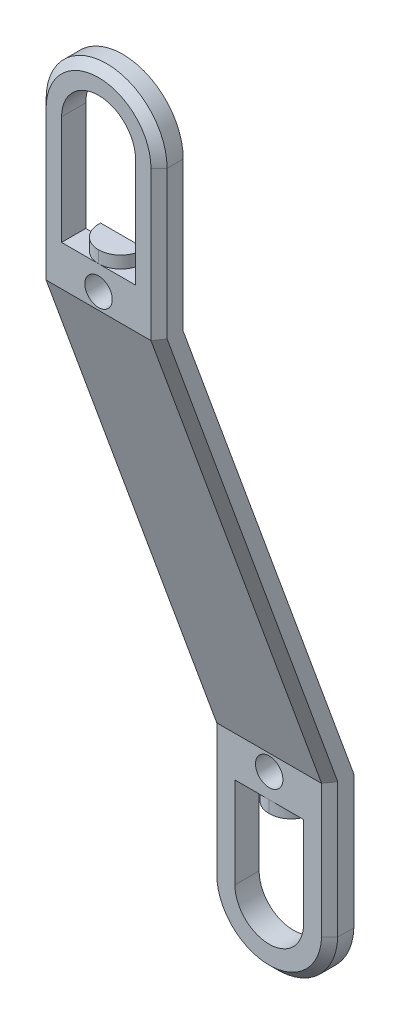
SolidWorks part; units mm, degrees
ref_plane "Front Plane" through (0, 0, 0) normal (0, 0, 1) x (1, 0, 0)
ref_plane "Top Plane" through (0, 0, 0) normal (0, 1, 0) x (1, 0, 0)
ref_plane "Right Plane" through (0, 0, 0) normal (1, 0, 0) x (0, 0, -1)
sketch "Sketch1" plane through (0, 0, 0) normal (0, 0, 1) x (1, 0, 0)
  line L0 (0, 42.5) -> (0, -42.5) construction
  line L1 (0, -14.3865) -> (0, 14.3865) construction
  line L2 (7.5, 42.5) -> (7.5, -42.5)
  line L3 (-7.5, 42.5) -> (-7.5, -42.5)
  line L4 (8.25, 0) -> (-8.25, 0) construction
  arc A0 (7.5, 42.5) -> (-7.5, 42.5) centre (0, 42.5) ccw
  arc A1 (-7.5, -42.5) -> (7.5, -42.5) centre (0, -42.5) ccw
  point P5 (0, 0)
  point P10 (0, 50)
  point P11 (0, -50)
  dimension "D1" = 100
  dimension "D2" = 15
extrude "Boss-Extrude1" add sketch "Sketch1" along normal blind 3
sketch "Sketch2" plane through (0, 0, 3) normal (0, 0, 1) x (1, 0, 0)
  line L0 (0, -14.3865) -> (0, 14.3865) construction
  line L1 (-4.585, 42.5) -> (-4.585, 29)
  line L2 (-4.585, 29) -> (4.585, 29)
  line L3 (4.585, 29) -> (4.585, 42.5)
  arc A0 (4.585, 42.5) -> (-4.585, 42.5) centre (0, 42.5) ccw
  arc A1 (7.5, 42.5) -> (-7.5, 42.5) centre (0, 42.5) ccw construction
  dimension "D1" = 13.5
extrude "Cut-Extrude1" cut sketch "Sketch2" against normal up to next
sketch "Sketch3" plane through (0, 29, 0) normal (0, 1, 0) x (1, 0, 0)
  line L0 (4.585, 0) -> (-4.585, 0) construction
  line L1 (-2.75, 0) -> (2.75, 0)
  line L2 (-2.75, 0) -> (-2.75, -3)
  line L3 (-2.75, -3) -> (2.75, -3)
  line L4 (2.75, 0) -> (2.75, -3)
  line L5 (-4.585, -3) -> (4.585, -3) construction
  line L6 (0, -14.3865) -> (0, 14.3865) construction
  point P8 (0, 0)
  dimension "D1" = 5.5
extrude "Boss-Extrude2" add sketch "Sketch3" along normal blind 1.5
mirror "Mirror1" about plane through (0, 0, 0) normal (0, 1, 0) of "Boss-Extrude2", "Cut-Extrude1"
sketch "Sketch4" plane through (0, 0, 0) normal (1, 0, 0) x (0, 0, -1)
  line L1 (-6.851, 24) -> (0, 24)
  line L2 (-6.851, 24) -> (-6.851, -55.5038)
  line L3 (-6.851, -55.5038) -> (0, -55.5038)
  line L4 (0, 24) -> (0, -55.5038)
  line L5 (0, 8.25) -> (0, -8.25) construction
  dimension "D1" = 5
extrude "Cut-Extrude2" cut sketch "Sketch4" against normal up to next and the other way up to next
sketch "Sketch5" plane through (0, 0, 0) normal (1, 0, 0) x (0, 0, -1)
  line L0 (0, 24) -> (21.1574, -34.1294)
  line L2 (-3, 24) -> (0, 24) construction
  line L3 (21.1574, -34.1294) -> (18.1574, -34.1294)
  line L4 (18.1574, -34.1294) -> (-3, 24)
  line L5 (-3, 24) -> (0, 24)
  line L6 (-3, 24) -> (-3, 42.5) construction
  dimension "D1" = 20
extrude "Boss-Extrude3" add sketch "Sketch5" along normal up to surface (7.5 mm away) and the other way up to vertex (7.5 mm away) up to face at (7.5, 33.25, 1.5) other way up to point (-7.5, 24, 0)
sketch "Sketch6" plane through (0, -34.1294, 0) normal (0, -1, 0) x (1, 0, 0)
  line L4 (-7.5, -21.1574) -> (7.5, -21.1574)
  line L5 (7.5, -21.1574) -> (7.5, -18.1574)
  line L6 (7.5, -18.1574) -> (-7.5, -18.1574)
  line L7 (-7.5, -18.1574) -> (-7.5, -21.1574)
  line L8 (-7.5, -21.1574) -> (7.5, -21.1574)
  line L9 (7.5, -21.1574) -> (7.5, -18.1574)
  line L10 (7.5, -18.1574) -> (-7.5, -18.1574)
  line L11 (-7.5, -18.1574) -> (-7.5, -21.1574)
  dimension "D1" = 0
ref_plane "Plane1" through (0, 0, -21.1574) normal (0, 0, 1) x (1, 0, 0)
sketch "Sketch7" plane through (0, 0, -21.1574) normal (0, 0, 1) x (1, 0, 0)
  line L0 (7.5, -34.1294) -> (7.5, -50.6294)
  line L1 (-7.5, -34.1294) -> (-7.5, -50.3954)
  line L6 (7.5, 24) -> (-7.5, 24)
  line L7 (7.5, -34.1294) -> (7.5, 24)
  line L8 (-7.5, -34.1294) -> (7.5, -34.1294)
  line L9 (-7.5, 24) -> (-7.5, -34.1294)
  line L12 (-7.5, -34.1294) -> (7.5, -34.1294)
  arc A0 (-7.5, -50.3954) -> (7.5, -50.6294) centre (0.0018, -50.3954) ccw
  dimension "D2" = 16.5
  dimension "D1" = 0
extrude "Boss-Extrude5" add sketch "Sketch7" along normal up to vertex (3 mm away) up to point (7.5, -34.1294, -18.1574)
sketch "Sketch9" plane through (0, 0, -21.1574) normal (0, 0, -1) x (-1, 0, 0)
  line L0 (-4.25, -39.1294) -> (4.25, -39.1294)
  line L1 (4.25, -39.1294) -> (4.25, -50.3954)
  line L3 (-4.25, -39.1294) -> (-4.2536, -50.394)
  line L4 (-7.5, -34.1294) -> (7.5, -34.1294) construction
  arc A0 (-4.2536, -50.394) -> (4.25, -50.3954) centre (-0.0018, -50.3954) ccw
  arc A2 (-7.5, -50.6294) -> (7.5, -50.3954) centre (-0.0018, -50.3954) ccw construction
  dimension "D1" = 8.5
  dimension "D3" = 5
extrude "Cut-Extrude3" cut sketch "Sketch9" against normal up to next
sketch "Sketch10" plane through (0, -39.1294, 0) normal (0, -1, 0) x (1, 0, 0)
  line L0 (-4.25, -18.1574) -> (4.25, -18.1574) construction
  line L1 (-2.75, -18.1574) -> (2.75, -18.1574)
  line L2 (-2.75, -18.1574) -> (-2.75, -21.1574)
  line L3 (-2.75, -21.1574) -> (2.75, -21.1574)
  line L4 (2.75, -18.1574) -> (2.75, -21.1574)
  line L5 (-4.25, -21.1574) -> (4.25, -21.1574) construction
  point P8 (0, -18.1574)
  point P9 (0, -18.1574)
  dimension "D1" = 5.5
extrude "Boss-Extrude6" add sketch "Sketch10" along normal blind 1.5
sketch "Sketch11" plane through (0, 0, 3) normal (0, 0, 1) x (1, 0, 0)
  line L0 (7.5, 24) -> (7.5, 42.5) construction
  line L1 (-7.5, 42.5) -> (-7.5, 24) construction
  line L2 (7.5, 24) -> (7.5, 42.5)
  line L3 (-7.5, 42.5) -> (-7.5, 24)
  line L4 (-5.5, 28) -> (5.5, 28)
  line L5 (5.5, 24) -> (5.5, 42.5)
  line L6 (-5.5, 42.5) -> (-5.5, 24)
  line L7 (5.5, 28) -> (5.5, 42.5)
  line L8 (-5.5, 42.5) -> (-5.5, 28)
  line L9 (7.5, 24) -> (-7.5, 24) construction
  line L10 (7.5, 24) -> (-7.5, 24)
  line L11 (-4.585, 29) -> (-2.75, 29) construction
  arc A0 (7.5, 42.5) -> (-7.5, 42.5) centre (0, 42.5) ccw construction
  arc A1 (7.5, 42.5) -> (-7.5, 42.5) centre (0, 42.5) ccw
  arc A4 (5.5, 42.5) -> (-5.5, 42.5) centre (0, 42.5) ccw
  arc A5 (5.5, 42.5) -> (-5.5, 42.5) centre (0, 42.5) ccw
  dimension "D2" = 1
  dimension "D1" = 2
extrude "Boss-Extrude7" [suppressed] add sketch "Sketch11" along normal blind 2
sketch "Sketch12" plane through (0, 0, -18.1574) normal (0, 0, 1) x (1, 0, 0)
  line L0 (-5.5, -38.1294) -> (-5.5, -50.3954)
  line L1 (5.5, -50.5957) -> (5.5, -38.1294)
  line L2 (-5.5, -38.1294) -> (5.5, -38.1294)
  line L3 (7.5, -34.1294) -> (-7.5, -34.1294)
  line L4 (-7.5, -34.1294) -> (-7.5, -50.3954)
  line L5 (7.5, -50.6294) -> (7.5, -34.1294)
  line L6 (7.5, -34.1294) -> (-7.5, -34.1294)
  line L7 (-7.5, -34.1294) -> (-7.5, -50.3954)
  line L8 (7.5, -50.6294) -> (7.5, -34.1294)
  line L9 (-5.5, -34.1294) -> (-5.5, -50.3954) construction
  line L10 (5.5, -50.5957) -> (5.5, -34.1294) construction
  line L11 (-4.25, -39.1294) -> (-2.75, -39.1294) construction
  arc A0 (-5.5, -50.3954) -> (5.5, -50.5957) centre (0.0018, -50.3954) ccw
  arc A1 (-7.5, -50.3954) -> (7.5, -50.6294) centre (0.0018, -50.3954) ccw
  arc A2 (-7.5, -50.3954) -> (7.5, -50.6294) centre (0.0018, -50.3954) ccw
  dimension "D3" = 1
  dimension "D1" = 0
  dimension "D2" = 2
extrude "Boss-Extrude8" [suppressed] add sketch "Sketch12" along normal blind 2
sketch "Sketch13" [suppressed] plane through (-7.5, 0, 0) normal (-1, 0, 0) x (0, 0, 1)
  line L0 (5, 24) -> (-16.1574, -34.1294)
  line L1 (-16.1574, -34.1294) -> (-18.1574, -34.1294) construction
  line L2 (-16.1574, -34.1294) -> (-18.1574, -34.1294)
  line L3 (3, 24) -> (-18.1574, -34.1294) construction
  line L4 (3, 24) -> (-18.1574, -34.1294)
  line L5 (5, 24) -> (3, 24) construction
  line L6 (5, 24) -> (3, 24)
extrude "Boss-Extrude9" [suppressed] add sketch "Sketch13" against normal up to surface (15 mm away) up to face at (7.5, -4.5647, -9.0787)
fillet "Fillet1" [suppressed] radius 2.75
fillet "Fillet2" radius 2.75 4 edges at (2.75, -39.8794, -18.1574) (-2.75, -39.8794, -18.1574) (-2.75, 29.75, 3) (2.75, 29.75, 3)
hole_wizard "M3 Clearance Hole1" positions "Sketch14" profile "Sketch15" hole size "M3" standard "ISO" end condition through all
sketch "Sketch14" plane through (0, 0, 0) normal (0, 0, -1) x (-1, 0, 0)
  line L0 (-7.5, 24) -> (7.5, 24) construction
  line L2 (0, 29) -> (0, 30.5) construction
  point P0 (0, 26)
  point P3 (0, 26)
  point P5 (0, 26)
  dimension "D1" = 2
sketch "Sketch15" plane through (0, 26, 0) normal (1, 0, 0) x (0, 1, 0)
  line L0 (0, 0) -> (0, 3)
  line L1 (0, 3) -> (1.7, 3)
  line L2 (1.7, 3) -> (1.7, 0.025)
  line L3 (1.7, 0.025) -> (1.725, 0)
  line L5 (1.725, 0) -> (0, 0)
  line L6 (-1.7, 0.025) -> (-1.725, 0) construction
  line L11 (0, -6.35) -> (0, 107.95) construction
  dimension "Thru Hole Dia." = 3.4
  dimension "Thru Hole Depth" = 3
  dimension "Near C'Sink Dia." = 3.45
  dimension "Near C'Sink Angle" = 90
hole_wizard "M3 Clearance Hole2" positions "Sketch16" profile "Sketch17" hole size "M3" standard "ISO" end condition through all
sketch "Sketch16" plane through (0, 0, -21.1574) normal (0, 0, -1) x (-1, 0, 0)
  line L0 (-7.5, -34.1294) -> (7.5, -34.1294) construction
  line L1 (0, -39.1294) -> (0, -40.6294) construction
  point P0 (0, -36.1294)
  dimension "D1" = 2
sketch "Sketch17" plane through (0, -36.1294, -21.1574) normal (1, 0, 0) x (0, 1, 0)
  line L0 (0, 0) -> (0, 24.1574)
  line L1 (0, 24.1574) -> (1.7, 24.1574)
  line L2 (1.7, 24.1574) -> (1.7, 0.025)
  line L3 (1.7, 0.025) -> (1.725, 0)
  line L5 (1.725, 0) -> (0, 0)
  line L6 (-1.7, 0.025) -> (-1.725, 0) construction
  line L11 (0, -6.35) -> (0, 107.95) construction
  dimension "Thru Hole Dia." = 3.4
  dimension "Thru Hole Depth" = 24.1574
  dimension "Near C'Sink Dia." = 3.45
  dimension "Near C'Sink Angle" = 90
sketch "Sketch19" plane through (-5.5, 0, 0) normal (1, 0, 0) x (0, 0, -1)
  line L4 (-3, 28) -> (-3, 42.5)
  line L5 (-3, 42.5) -> (-5, 42.5)
  line L6 (-5, 42.5) -> (-5, 28)
  line L7 (-5, 28) -> (-3, 28)
  line L8 (-3, 28) -> (-3, 42.5)
  line L9 (-3, 42.5) -> (-5, 42.5)
  line L10 (-5, 42.5) -> (-5, 28)
  line L11 (-5, 28) -> (-3, 28)
  dimension "D1" = 0
extrude "Cut-Extrude4" [suppressed] cut sketch "Sketch19" against normal up to next and the other way blind 50
sketch "Sketch20" plane through (-5.5, 0, 0) normal (1, 0, 0) x (0, 0, -1)
  line L4 (18.1574, -50.3954) -> (18.1574, -38.1294)
  line L5 (18.1574, -38.1294) -> (16.1574, -38.1294)
  line L6 (16.1574, -38.1294) -> (16.1574, -50.3954)
  line L7 (16.1574, -50.3954) -> (18.1574, -50.3954)
  line L8 (18.1574, -50.3954) -> (18.1574, -38.1294)
  line L9 (18.1574, -38.1294) -> (16.1574, -38.1294)
  line L10 (16.1574, -38.1294) -> (16.1574, -50.3954)
  line L11 (16.1574, -50.3954) -> (18.1574, -50.3954)
  dimension "D1" = 0
extrude "Cut-Extrude5" [suppressed] cut sketch "Sketch20" against normal through all both and the other way through all
chamfer "Chamfer1" [suppressed] distance 1 angle 45
chamfer "Chamfer2" distance 1 angle 45 8 edges at (-0.1152, -57.8963, -18.1574) (7.5, -42.3794, -18.1574) (-7.5, -42.2624, -18.1574) (-7.5, -5.0647, -7.5787) (-7.5, 33.25, 3) (0, 50, 3) (7.5, -5.0647, -7.5787) (7.5, 33.25, 3)
